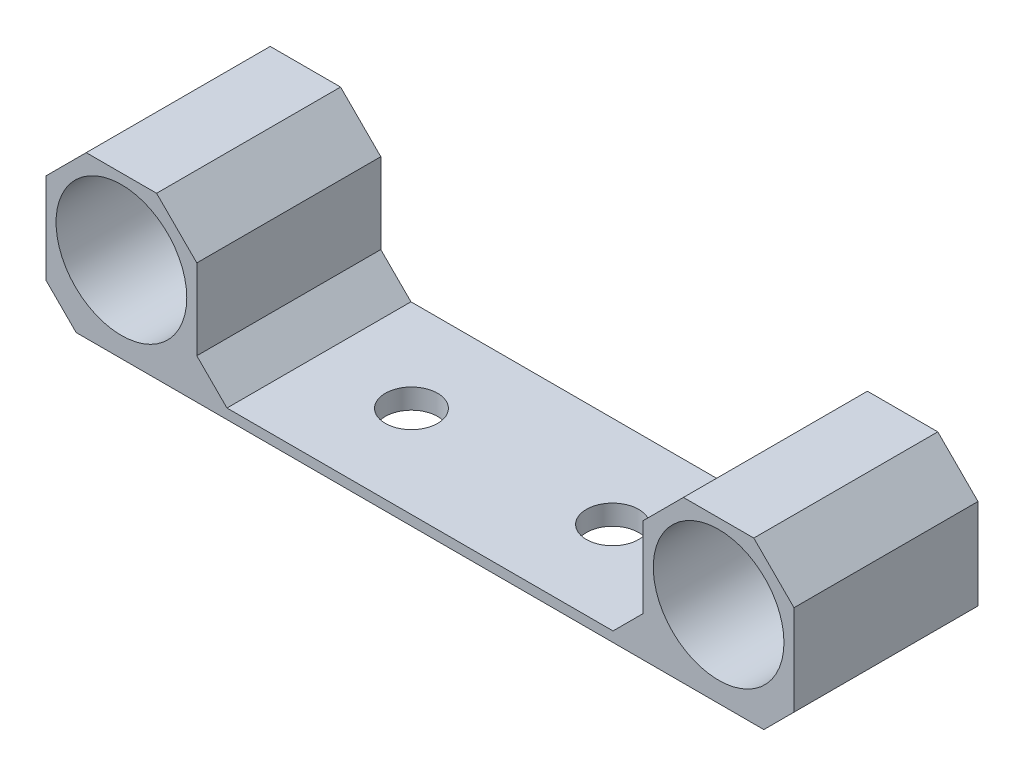
SolidWorks part; units mm, degrees
ref_plane "Front Plane" through (0, 0, 0) normal (0, 0, 1) x (1, 0, 0)
ref_plane "Top Plane" through (0, 0, 0) normal (0, 1, 0) x (1, 0, 0)
ref_plane "Right Plane" through (0, 0, 0) normal (1, 0, 0) x (0, 0, -1)
sketch "Sketch1" plane through (0, 0, 0) normal (0, 1, 0) x (1, 0, 0)
  line L0 (22.2, 18.3) -> (22.2, 0) construction
  line L1 (0, 0) -> (44.4, 0)
  line L2 (0, 0) -> (0, 18.3)
  line L3 (0, 18.3) -> (44.4, 18.3)
  line L4 (44.4, 0) -> (44.4, 18.3)
  line L5 (12.2, 9.15) -> (22.2, 9.15) construction
  line L6 (22.2, 9.15) -> (32.2, 9.15) construction
  line L8 (44.4, 0) -> (59.4, 0)
  line L9 (44.4, 0) -> (44.4, 18.3)
  line L10 (44.4, 18.3) -> (59.4, 18.3)
  line L11 (59.4, 0) -> (59.4, 18.3)
  line L12 (0, 0) -> (-15, 0)
  line L13 (0, 0) -> (0, 18.3)
  line L14 (0, 18.3) -> (-15, 18.3)
  line L15 (-15, 0) -> (-15, 18.3)
  circle A0 centre (12.2, 9.15) radius 2.6
  circle A1 centre (32.2, 9.15) radius 2.6
  dimension "D3" = 5.2
  dimension "D4" = 5.2
  dimension "D1" = 18.3
  dimension "D2" = 44.4
  dimension "D5" = 10
  dimension "D6" = 10
  dimension "D7" = 15
  dimension "D8" = 15
extrude "Boss-Extrude1" add sketch "Sketch1" along normal blind 2 contours L15 L12 L2 L14 | L1 L4 L3 L2 A1 A0 | L8 L11 L10 L4 region at (22.2, 0, -9.15) region at (-7.5, 0, -9.15) region at (51.9, 0, -9.15)
extrude "Boss-Extrude2" add sketch "Sketch1<3>" along normal blind 17 contours L8 L11 L10 L4 | L15 L12 L2 L14 region at (-7.5, 0, -9.15) region at (51.9, 0, -9.15)
sketch "Sketch1<3>" plane through (0, 0, 0) normal (0, 1, 0) x (1, 0, 0) same geometry as "Sketch1"
sketch "Sketch2" plane through (0, 0, 0) normal (0, 0, 1) x (1, 0, 0)
  line L0 (-15, 9.5) -> (0, 9.5) construction
  line L1 (0, 2) -> (-15, 2)
  line L2 (0, 2) -> (0, 17)
  line L3 (0, 17) -> (-15, 17)
  line L4 (-15, 2) -> (-15, 17)
  line L5 (44.4, 2) -> (59.4, 2)
  line L6 (44.4, 2) -> (44.4, 17)
  line L7 (44.4, 17) -> (59.4, 17)
  line L8 (59.4, 2) -> (59.4, 17)
  line L9 (44.4, 9.5) -> (59.4, 9.5) construction
  circle A0 centre (-7.5, 9.5) radius 6.5
  circle A1 centre (51.9, 9.5) radius 6.5
  dimension "D1" = 13
  dimension "D2" = 13
extrude "Cut-Extrude2" cut sketch "Sketch2" against normal offset from surface (12.315 mm away) 5.985 contours A0 | A1 up to face at (22.2, 9, -18.3)
fillet "Fillet3" radius 4 6 edges at (59.4, 0, -9.15) (59.4, 17, -9.15) (44.4, 17, -9.15) (-15, 0, -9.15) (0, 17, -9.15) (-15, 17, -9.15) profile chamfer
fillet "Fillet4" radius 3 2 edges at (44.4, 2, -9.15) (0, 2, -9.15) profile chamfer
chamfer "Chamfer2" distance 1 angle 45 2 edges at (22.2, 0, -18.3) (22.2, 0, 0)
